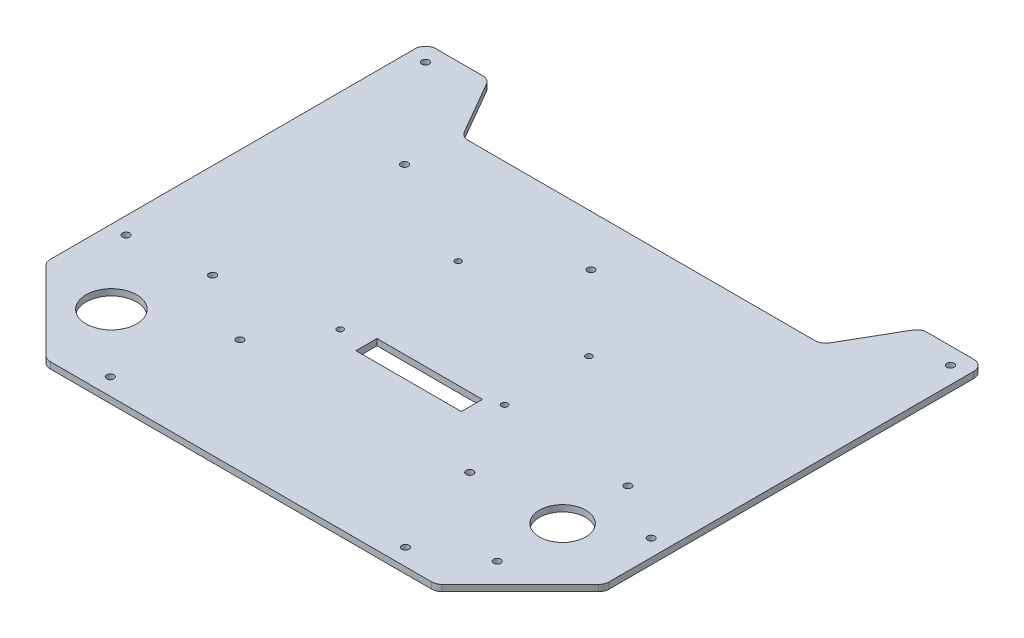
SolidWorks part; units mm, degrees
material "Acier non allié"
ref_plane "Front" through (0, 0, 0) normal (0, 0, 1) x (1, 0, 0)
ref_plane "Top" through (0, 0, 0) normal (0, 1, 0) x (1, 0, 0)
ref_plane "Right" through (0, 0, 0) normal (1, 0, 0) x (0, 0, -1)
sketch "Esquisse1" plane through (0, 0, 0) normal (0, 1, 0) x (1, 0, 0)
  line L0 (0, 0) -> (0, 1919.0564) construction
  line L1 (-92.5, 0) -> (92.5, 0)
  line L2 (92.5, 0) -> (132.5, 40)
  line L3 (132.5, 40) -> (132.5, 220)
  line L4 (132.5, 220) -> (102.5, 220)
  line L5 (102.5, 220) -> (85.1795, 190)
  line L6 (85.1795, 190) -> (-85.1795, 190)
  line L7 (-102.5, 220) -> (-85.1795, 190)
  line L8 (-132.5, 220) -> (-102.5, 220)
  line L9 (-132.5, 40) -> (-132.5, 220)
  line L10 (-92.5, 0) -> (-132.5, 40)
  point P12 (0, 190)
  dimension "D1" = 132.5
  dimension "D2" = 220
  dimension "D3" = 30
  dimension "D4" = 30
  dimension "D5" = 40
  dimension "D6" = 40
  dimension "D7" = 60
extrude "Boss.-Extru.1" add sketch "Esquisse1" along normal blind 3
fillet "Congé1" radius 5 10 edges at (132.5, 1.5, -220) (102.5, 1.5, -220) (85.1795, 1.5, -190) (-85.1795, 1.5, -190) (-102.5, 1.5, -220) (-132.5, 1.5, -220) (-132.5, 1.5, -40) (-92.5, 1.5, 0) (92.5, 1.5, 0) (132.5, 1.5, -40)
sketch "Esquisse2" plane through (0, 0, 0) normal (0, -1, 0) x (1, 0, 0)
  line L0 (0, 0) -> (0, -330.9968) construction
  line L1 (-90.4289, 0) -> (90.4289, 0) construction
  line L2 (-105.3868, -220) -> (-127.5, -220) construction
  line L3 (-132.5, -215) -> (-132.5, -42.0711) construction
  circle A0 centre (-70, -8) radius 1
  circle A1 centre (-124.5, -70) radius 1
  circle A2 centre (-124.5, -212) radius 1
  circle A3 centre (124.5, -212) radius 1
  circle A4 centre (124.5, -70) radius 1
  circle A5 centre (70, -8) radius 1
  dimension "D3" = 2
  dimension "D6" = 2
  dimension "D9" = 2
  dimension "D1" = 70
  dimension "D2" = 8
  dimension "D4" = 124.5
  dimension "D5" = 70
  dimension "D7" = 8
  dimension "D8" = 8
extrude "Enlèv. mat.-Extru.1" cut sketch "Esquisse2" against normal through all
hole_wizard "Dégagement M31" positions "Esquisse3" profile "Esquisse4" hole size "M3" standard "ISO" end condition through all
sketch "Esquisse3" plane through (0, 0, 0) normal (0, -1, 0) x (-1, 0, 0)
  point P0 (-70, 8)
  point P3 (-124.5, 70)
  point P6 (-124.5, 212)
  point P9 (124.5, 212)
  point P12 (124.5, 70)
  point P15 (70, 8)
sketch "Esquisse4" plane through (70, 0, -8) normal (1, 0, 0) x (0, 0, -1)
  line L0 (0, 0) -> (0, 3)
  line L1 (0, 3) -> (1.7, 3)
  line L2 (1.7, 3) -> (1.7, 0)
  line L5 (1.7, 0) -> (0, 0)
  line L11 (0, -6.35) -> (0, 107.95) construction
  dimension "Diamètre du perçage jusqu'au prochain" = 3.4
  dimension "Profondeur du perçage jusqu'au prochain" = 3
sketch "Esquisse5" plane through (0, 0, 0) normal (0, -1, 0) x (1, 0, 0)
  line L0 (-35, -138) -> (-35, -82) construction
  line L5 (35, -130) -> (35, -90) construction
  line L6 (132.5, -42.0711) -> (132.5, -215) construction
  line L7 (97.5, -86) -> (97.5, -24) construction
  line L20 (-132.5, -215) -> (-132.5, -42.0711) construction
  line L21 (-90.4289, 0) -> (90.4289, 0) construction
  line L22 (-105.3868, -220) -> (-127.5, -220) construction
  line L27 (-132.5, -215) -> (-132.5, -42.0711) construction
  line L28 (127.5, -220) -> (105.3868, -220) construction
  line L29 (-54.5, -54) -> (54.5, -54) construction
  line L30 (-54.5, -54) -> (-54.5, -166) construction
  line L31 (-54.5, -166) -> (54.5, -166) construction
  line L32 (54.5, -54) -> (54.5, -166) construction
  line L33 (-87.5, -74) -> (-87.5, -165) construction
  line L34 (-22.5, -87) -> (27.5, -87)
  line L35 (-22.5, -87) -> (-22.5, -77)
  line L36 (-22.5, -77) -> (27.5, -77)
  line L37 (27.5, -87) -> (27.5, -77)
  line L39 (127.5, -220) -> (105.3868, -220) construction
  circle A0 centre (-97.5, -36) radius 12
  circle A3 centre (97.5, -55) radius 11
  circle A4 centre (97.5, -86) radius 1.5
  circle A5 centre (97.5, -24) radius 1.5
  circle A6 centre (-35, -138) radius 1
  circle A7 centre (-35, -82) radius 1
  circle A8 centre (35, -130) radius 1
  circle A9 centre (35, -90) radius 1
  circle A10 centre (0, -166) radius 1.5
  circle A11 centre (-54.5, -54) radius 1.5
  circle A12 centre (54.5, -54) radius 1.5
  circle A13 centre (-87.5, -74) radius 1.5
  circle A14 centre (-87.5, -165) radius 1.5
  point P8 (97.5, -55)
  point P18 (-35, -110)
  point P23 (0, -166)
  point P29 (54.5, -110)
  point P47 (-22.5, -82)
  point P48 (2.5, -77)
  dimension "D10" = 24
  dimension "D2" = 22
  dimension "D6" = 3
  dimension "D7" = 3
  dimension "D20" = 2
  dimension "D21" = 2
  dimension "D27" = 2
  dimension "D28" = 2
  dimension "D14" = 3
  dimension "D30" = 3
  dimension "D31" = 3
  dimension "D38" = 3
  dimension "D39" = 3
  dimension "D8" = 35
  dimension "D9" = 36
  dimension "D3" = 35
  dimension "D4" = 55
  dimension "D5" = 62
  dimension "D22" = 110
  dimension "D23" = 97.5
  dimension "D24" = 56
  dimension "D25" = 8
  dimension "D26" = 40
  dimension "D29" = 70
  dimension "D11" = 109
  dimension "D12" = 112
  dimension "D13" = 110
  dimension "D32" = 50
  dimension "D33" = 10
  dimension "D34" = 135
  dimension "D35" = 91
  dimension "D37" = 55
  dimension "D15" = 45
extrude "Enlèv. mat.-Extru.2" cut sketch "Esquisse5" against normal through all
fillet "Congé2" [suppressed] radius 3
hole_wizard "Dégagement M32" positions "Esquisse6" profile "Esquisse7" hole size "M3" standard "ISO" end condition up to next
sketch "Esquisse6" plane through (0, 3, 0) normal (0, 1, 0) x (1, 0, 0)
  point P7 (97.5, 86)
  point P10 (97.5, 24)
  point P13 (-54.5, 54)
  point P16 (54.5, 54)
  point P19 (0, 166)
  point P24 (-87.5, 74)
  point P27 (-87.5, 165)
sketch "Esquisse7" plane through (97.5, 3, -86) normal (1, 0, 0) x (0, 0, 1)
  line L0 (0, 0) -> (0, 3)
  line L1 (0, 3) -> (1.7, 3)
  line L2 (1.7, 3) -> (1.7, 0)
  line L5 (1.7, 0) -> (0, 0)
  line L11 (0, -6.35) -> (0, 107.95) construction
  dimension "Diamètre du perçage jusqu'au prochain" = 3.4
  dimension "Profondeur du perçage jusqu'au prochain" = 3
hole_wizard "Dégagement M2.51" positions "Esquisse8" profile "Esquisse9" hole size "M2.5" standard "ISO" end condition up to next
sketch "Esquisse8" plane through (0, 3, 0) normal (0, 1, 0) x (1, 0, 0)
  point P0 (-35, 138)
  point P3 (-35, 82)
  point P6 (35, 90)
  point P9 (35, 130)
sketch "Esquisse9" plane through (-35, 3, -138) normal (1, 0, 0) x (0, 0, 1)
  line L0 (0, 0) -> (0, 3)
  line L1 (0, 3) -> (1.45, 3)
  line L2 (1.45, 3) -> (1.45, 0)
  line L5 (1.45, 0) -> (0, 0)
  line L11 (0, -6.35) -> (0, 107.95) construction
  dimension "Diamètre du perçage jusqu'au prochain" = 2.9
  dimension "Profondeur du perçage jusqu'au prochain" = 3
equation "\"WIDTH\"= 300mm'Total width of the robot"
equation "\"LENGTH\"= 220mm'Total length of the robot"
equation "\"CUT_DEPTH\"= 45mm'Depth of the cut on the edges of the plate"
equation "\"Plate_th\"= 3mm'Thickness of the plate"
equation "\"D1\"= \"Plate_th\""
equation "\"D23@Esquisse5\"=(265-70)/2"
